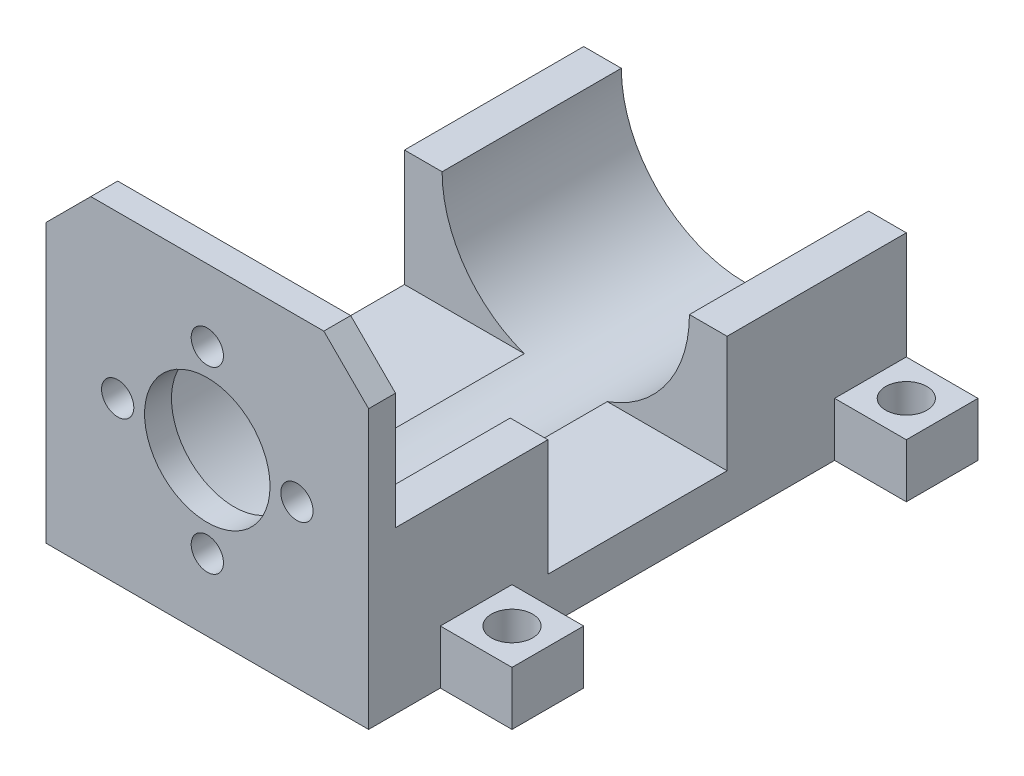
SolidWorks part; units mm, degrees
note: The reader was unsure of these and kept them because the rebuilt part matched: shared geometry of "Esquisse1<3>".
ref_plane "Plan de face" through (0, 0, 0) normal (0, 0, 1) x (1, 0, 0)
ref_plane "Plan de dessus" through (0, 0, 0) normal (0, 1, 0) x (1, 0, 0)
ref_plane "Plan de droite" through (0, 0, 0) normal (1, 0, 0) x (0, 0, -1)
sketch "Esquisse1" plane through (0, 0, 0) normal (0, 0, 1) x (1, 0, 0)
  line L0 (0, 0) -> (-10, 0) construction
  line L1 (-10, 0) -> (10, 0) construction
  line L2 (10, 0) -> (0, 0) construction
  line L3 (0, 0) -> (0, 10) construction
  line L4 (0, 0) -> (0, -10) construction
  line L5 (-18, 0) -> (-18, -18)
  line L6 (-18, -18) -> (0, -18)
  line L7 (0, -18) -> (18, -18)
  line L8 (18, -18) -> (18, 0)
  line L10 (18, 18) -> (-18, 18)
  line L11 (-18, 18) -> (-18, 0)
  line L12 (-18, 18) -> (-18, 13)
  line L13 (-18, 13) -> (-18, 18)
  line L14 (-18, 18) -> (-13, 18)
  line L15 (-13, 18) -> (-18, 13)
  line L16 (18, 18) -> (13, 18)
  line L17 (13, 18) -> (18, 18)
  line L18 (18, 18) -> (18, 13)
  line L19 (18, 13) -> (18, 0)
  line L20 (13, 18) -> (18, 13)
  line L21 (-18, 0) -> (-13.8, 0)
  line L22 (18, 0) -> (13.8, 0)
  circle A0 centre (0, 0) radius 13.8
  circle A1 centre (0, 0) radius 18
  circle A2 centre (-10, 0) radius 1.8
  circle A3 centre (0, 10) radius 1.8
  circle A4 centre (10, 0) radius 1.8
  circle A5 centre (0, -10) radius 1.8
  circle A6 centre (0, 0) radius 7
extrude "Boss.-Extru.1" add sketch "Esquisse1" against normal blind 60 contours A1 L7 L8 | A1 L5 L6 | L21 A1 L22 A0
extrude "Boss.-Extru.2" add sketch "Esquisse1<3>" against normal blind 3 contours A0 A5 A4 A3 A2 | L22 A1 L21 A0 | A1 L19 L20 L10 | A1 L10 L15 L11
sketch "Esquisse1<3>" plane through (0, 0, 0) normal (0, 0, 1) x (1, 0, 0) same geometry as "Esquisse1"
sketch "Esquisse2" plane through (0, -18, 0) normal (0, -1, 0) x (1, 0, 0)
  line L3 (18, -60) -> (26, -60)
  line L5 (-18, -60) -> (-26, -60)
  line L6 (-26, -60) -> (-26, -52)
  line L7 (-26, -52) -> (-18, -52)
  line L8 (-18, -52) -> (-18, -60)
  line L12 (26, -60) -> (26, -52)
  line L14 (-26, -52) -> (-18, -60) construction
  line L15 (-18, -52) -> (-26, -60) construction
  line L23 (-18, -60) -> (-18, 0) construction
  line L26 (26, -8) -> (18, -8)
  line L27 (18, -60) -> (18, 0) construction
  line L29 (26, -52) -> (18, -52)
  line L33 (-18, -16) -> (-18, 0)
  line L34 (-26, -8) -> (-18, -8)
  line L35 (18, -52) -> (18, -60)
  line L38 (18, -52) -> (26, -60) construction
  line L39 (26, -52) -> (18, -60) construction
  line L40 (-26, -8) -> (-26, -16)
  line L43 (-26, -16) -> (-18, -16)
  line L44 (-26, -8) -> (-18, -16) construction
  line L45 (-18, -8) -> (-26, -16) construction
  line L46 (26, -8) -> (26, -16)
  line L47 (26, -16) -> (18, -16)
  line L48 (18, -16) -> (18, -8)
  line L49 (18, -8) -> (26, -16) construction
  line L50 (26, -8) -> (18, -16) construction
  circle A5 centre (-22, -56) radius 2.3
  circle A11 centre (22, -56) radius 2.3
  circle A12 centre (-22, -12) radius 2.3
  circle A13 centre (22, -12) radius 2.3
sketch "Esquisse3" plane through (-18, 0, 0) normal (-1, 0, 0) x (0, 0, 1)
  line L0 (-60, -18) -> (0, -18) construction
  line L1 (-30, -18) -> (-30, 0) construction
  line L2 (-60, 0) -> (-3, 0) construction
  line L3 (-30, 0) -> (-20, 0)
  line L4 (-30, 0) -> (-40, 0)
  line L5 (-40, 0) -> (-40, -18) construction
  line L6 (-40, -18) -> (-30, -18) construction
  line L7 (-30, -18) -> (-20, -18) construction
  line L8 (-20, -18) -> (-20, 0) construction
  line L9 (-40, -18) -> (-40, -13) construction
  line L10 (-40, -13) -> (-20, -13)
  line L11 (-20, -13) -> (-20, 0)
  line L12 (-40, -13) -> (-40, 0)
extrude "Enlèv. mat.-Extru.2" cut sketch "Esquisse3" against normal blind 50
extrude "Boss.-Extru.4" add sketch "Esquisse2" against normal blind 6
